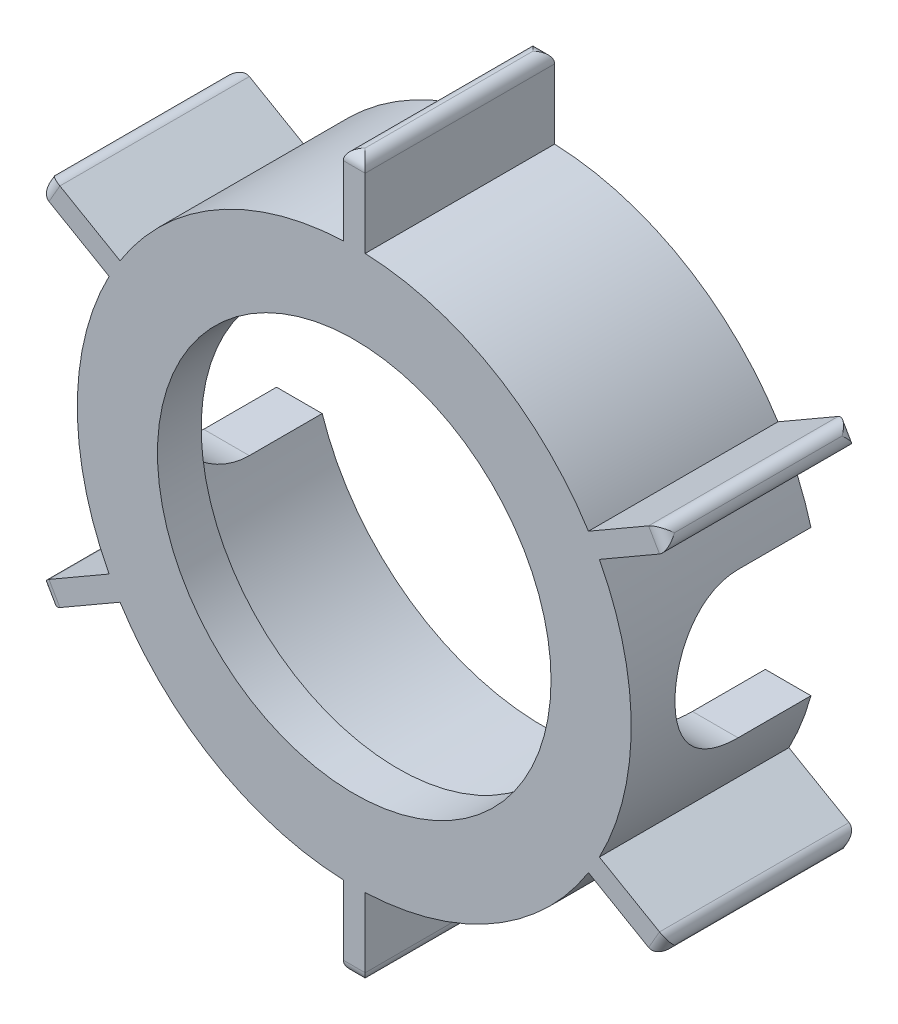
SolidWorks part; units mm, degrees
ref_plane "Plan de face" through (0, 0, 0) normal (0, 0, 1) x (1, 0, 0)
ref_plane "Plan de dessus" through (0, 0, 0) normal (0, 1, 0) x (1, 0, 0)
ref_plane "Plan de droite" through (0, 0, 0) normal (1, 0, 0) x (0, 0, -1)
sketch "Contour" plane through (0, 0, 0) normal (0, 0, 1) x (1, 0, 0)
  circle A0 centre (0, 0) radius 19
  dimension "D1" = 38
extrude "Boss.-Extru.1_Contour" add sketch "Contour" along normal blind 13
shell "Coque1" thickness 3 removed face at (19, 0, 0)
ref_plane "Plan1_Aimants" through (19, 0, 0) normal (1, 0, 0) x (0, 0, -1)
sketch "Ouvertue_aimant" plane through (19, 0, 0) normal (1, 0, 0) x (0, 0, -1)
  line L0 (-5, 5) -> (0, 5) construction
  line L6 (-10, 0) -> (0, 0) construction
  line L7 (-10, -16) -> (-10, 16) construction
  line L9 (0, -19) -> (0, 19) construction
  line L13 (-5, -5) -> (0, -5) construction
  line L14 (0, 5) -> (-5, 5)
  line L15 (-5, -5) -> (0, -5)
  line L16 (0, -5) -> (0, 5)
  circle A4 centre (-5, 0) radius 5 construction
  arc A5 (-5, 5) -> (-5, -5) centre (-5, 0) ccw
  dimension "D1" = 10
extrude "Enlèv. mat.-Extru.1_Ouvertue_aimant" cut sketch "Ouvertue_aimant" against normal up to next
mirror "Symétrie1_Ouvertue_aimant" about plane through (0, 0, 0) normal (1, 0, 0) of "Enlèv. mat.-Extru.1_Ouvertue_aimant"
sketch "Ouverture_Écrou" plane through (0, 0, 13) normal (0, 0, 1) x (1, 0, 0)
  circle A0 centre (0, 0) radius 13.5
  dimension "D1" = 27
extrude "Enlèv. mat.-Extru.2_Ouverture_Écrou" cut sketch "Ouverture_Écrou" against normal up to next
ref_axis "Axe1" through (0, 0, 13.65) along (0, 0, -1)
ref_plane "Plan1" through (0, 24.5, 0) normal (0, 1, 0) x (1, 0, 0)
sketch "Ailettes" plane through (0, 24.5, 0) normal (0, 1, 0) x (1, 0, 0)
  line L0 (-23.4499, 0) -> (23.4499, 0) construction
  line L1 (-0.75, 0) -> (0.75, 0)
  line L2 (-0.75, 0) -> (-0.75, -13)
  line L3 (-0.75, -13) -> (0.75, -13)
  line L4 (0.75, 0) -> (0.75, -13)
  line L5 (-0.75, 0) -> (0.75, -13) construction
  line L6 (-0.75, -13) -> (0.75, 0) construction
  line L7 (-19, -13) -> (19, -13) construction
  line L8 (0, -7.15) -> (0, 7.15) construction
  point P4 (0, -6.5)
  dimension "D1" = 1.5
extrude "Boss.-Extru.2_Ailettes" add sketch "Ailettes" against normal up to next
pattern_circular "Répétition circulaire4_Ailettes" count 6 over 360 about axis through (0, 0, 13) along (0, 0, -1) of "Boss.-Extru.2_Ailettes"
fillet "Congé1_Ailettes" radius 0.75 24 edges at (-20.8426, -12.8995, 6.5) (-21.2176, -12.25, 13) (-21.5926, -11.6005, 6.5) (-21.2176, -12.25, 0) (-21.5926, 11.6005, 6.5) (-21.2176, 12.25, 13) (-20.8426, 12.8995, 6.5) (-21.2176, 12.25, 0) (-0.75, 24.5, 6.5) (0, 24.5, 13) (0.75, 24.5, 6.5) (0, 24.5, 0) (20.8426, 12.8995, 6.5) (21.2176, 12.25, 13) (21.5926, 11.6005, 6.5) (21.2176, 12.25, 0) (21.5926, -11.6005, 6.5) (21.2176, -12.25, 13) (20.8426, -12.8995, 6.5) (21.2176, -12.25, 0) (0.75, -24.5, 6.5) (0, -24.5, 13) (-0.75, -24.5, 6.5) (0, -24.5, 0)
sketch "Esquisse1" plane through (0, 0, 0) normal (0, 0, -1) x (-1, 0, 0)
  line L0 (0, 24.5) -> (0, -24.5) construction
equation "\"D1@Congé1_Ailettes\"=1.5 / 2"
